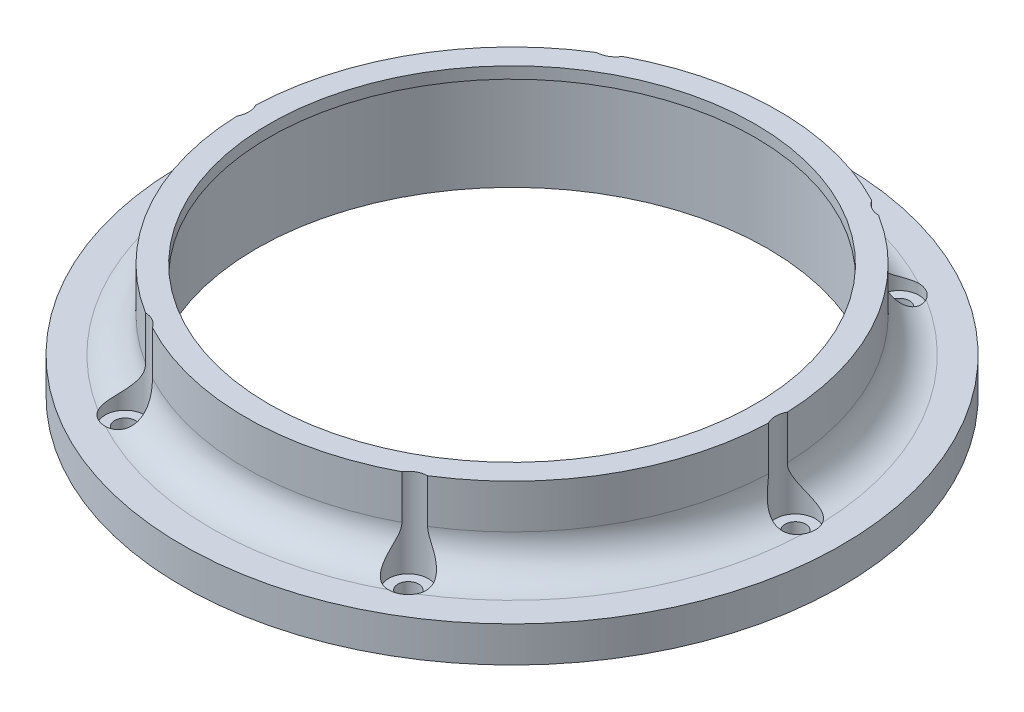
SolidWorks part; units mm, degrees
ref_plane "Front Plane" through (0, 0, 0) normal (0, 0, 1) x (1, 0, 0)
ref_plane "Top Plane" through (0, 0, 0) normal (0, 1, 0) x (1, 0, 0)
ref_plane "Right Plane" through (0, 0, 0) normal (1, 0, 0) x (0, 0, -1)
sketch "Sketch1" plane through (0, 0, 0) normal (0, 1, 0) x (1, 0, 0)
  circle A0 centre (0, 0) radius 61.25 construction
  circle A1 centre (0, 0) radius 55.25
  circle A2 centre (0, 0) radius 57.5
  dimension "D1" = 122.5
  dimension "D2" = 110.5
  dimension "D3" = 115
extrude "Boss-Extrude1" add sketch "Sketch1" along normal blind 22
sketch "Sketch2" plane through (0, 0, 0) normal (0, -1, 0) x (1, 0, 0)
  circle A0 centre (0, 0) radius 61.25 construction
  circle A1 centre (0, 0) radius 71.25
  circle A2 centre (0, 0) radius 57.5 construction
  circle A3 centre (0, 0) radius 57.5
  dimension "D1" = 122.5
  dimension "D2" = 10
extrude "Boss-Extrude2" add sketch "Sketch2" against normal blind 7.5
sketch "Sketch6" plane through (0, 7.5, 0) normal (0, 1, 0) x (1, 0, 0)
  circle A0 centre (0, 0) radius 61.25 construction
  point P0 (-61.25, 0)
  dimension "D1" = 122.5
hole_wizard "CBORE for M4 SBHCS1" positions "Sketch6" profile "Sketch5" counterbore size "M4" standard "ANSI Metric" end condition through all
sketch "Sketch5" plane through (-61.25, 7.5, 0) normal (1, 0, 0) x (0, 0, 1)
  line L0 (0, 0) -> (0, 7.5)
  line L1 (0, 7.5) -> (2.25, 7.5)
  line L3 (2.25, 7.5) -> (2.25, 2.2)
  line L4 (2.25, 2.2) -> (4.3, 2.2)
  line L5 (4.3, 2.2) -> (4.3, 0)
  line L7 (4.3, 0) -> (0, 0)
  line L11 (0, -6.35) -> (0, 107.95) construction
  dimension "Thru Hole Dia." = 4.5
  dimension "Thru Hole Depth" = 7.5
  dimension "C'Bore Dia." = 8.6
  dimension "C'Bore Depth" = 2.2
fillet "Fillet2" radius 7.5 1 edges at (57.5, 7.5, 0)
sketch "Sketch7" plane through (0, 7.5, 0) normal (0, 1, 0) x (1, 0, 0)
  circle A1 centre (-61.25, 0) radius 4.3
  circle A2 centre (-61.25, 0) radius 4.3
  dimension "D1" = 0
extrude "Cut-Extrude1" cut sketch "Sketch7" along normal through all
pattern_circular "CirPattern1" count 6 over 360 about axis through (0, 7.5, 0) along (0, -1, 0) of "Cut-Extrude1", "CBORE for M4 SBHCS1"
sketch "Sketch8" plane through (0, 22, 0) normal (0, 1, 0) x (1, 0, 0)
  circle A0 centre (0, 0) radius 52.5
  arc A12 (-57.4639, -2.0384) -> (-30.4972, -48.746) centre (0, 0) ccw
  arc A13 (-26.9666, -50.7844) -> (-30.4972, -48.746) centre (-30.625, -53.0441) ccw
  arc A14 (-26.9666, -50.7844) -> (26.9666, -50.7844) centre (0, 0) ccw
  arc A15 (30.4972, -48.746) -> (26.9666, -50.7844) centre (30.625, -53.0441) ccw
  arc A16 (30.4972, -48.746) -> (57.4639, -2.0384) centre (0, 0) ccw
  arc A17 (57.4639, 2.0384) -> (57.4639, -2.0384) centre (61.25, 0) ccw
  arc A18 (57.4639, 2.0384) -> (30.4972, 48.746) centre (0, 0) ccw
  arc A19 (26.9666, 50.7844) -> (30.4972, 48.746) centre (30.625, 53.0441) ccw
  arc A20 (26.9666, 50.7844) -> (-26.9666, 50.7844) centre (0, 0) ccw
  arc A21 (-30.4972, 48.746) -> (-26.9666, 50.7844) centre (-30.625, 53.0441) ccw
  arc A22 (-30.4972, 48.746) -> (-57.4639, 2.0384) centre (0, 0) ccw
  arc A23 (-57.4639, -2.0384) -> (-57.4639, 2.0384) centre (-61.25, 0) ccw
  arc A24 (-57.4639, -2.0384) -> (-30.4972, -48.746) centre (0, 0) ccw
  arc A25 (-26.9666, -50.7844) -> (-30.4972, -48.746) centre (-30.625, -53.0441) ccw
  arc A26 (-26.9666, -50.7844) -> (26.9666, -50.7844) centre (0, 0) ccw
  arc A27 (30.4972, -48.746) -> (26.9666, -50.7844) centre (30.625, -53.0441) ccw
  arc A28 (30.4972, -48.746) -> (57.4639, -2.0384) centre (0, 0) ccw
  arc A29 (57.4639, 2.0384) -> (57.4639, -2.0384) centre (61.25, 0) ccw
  arc A30 (57.4639, 2.0384) -> (30.4972, 48.746) centre (0, 0) ccw
  arc A31 (26.9666, 50.7844) -> (30.4972, 48.746) centre (30.625, 53.0441) ccw
  arc A32 (26.9666, 50.7844) -> (-26.9666, 50.7844) centre (0, 0) ccw
  arc A33 (-30.4972, 48.746) -> (-26.9666, 50.7844) centre (-30.625, 53.0441) ccw
  arc A34 (-30.4972, 48.746) -> (-57.4639, 2.0384) centre (0, 0) ccw
  arc A35 (-57.4639, -2.0384) -> (-57.4639, 2.0384) centre (-61.25, 0) ccw
  dimension "D2" = 5
  dimension "D1" = 0
extrude "Boss-Extrude3" add sketch "Sketch8" along normal blind 2.5
sketch "Sketch10" plane through (0, 0, 0) normal (0, -1, 0) x (1, 0, 0)
  circle A0 centre (0, 0) radius 55.25 construction
  circle A1 centre (0, 0) radius 71.25
  circle A2 centre (0, 0) radius 71.25
  circle A3 centre (61.25, 0) radius 2.25 construction
  circle A4 centre (30.625, 53.0441) radius 2.25 construction
  circle A5 centre (-30.625, 53.0441) radius 2.25 construction
  circle A6 centre (-61.25, 0) radius 2.25 construction
  circle A7 centre (-30.625, -53.0441) radius 2.25 construction
  circle A8 centre (30.625, -53.0441) radius 2.25 construction
  circle A9 centre (0, 0) radius 55.25
  circle A10 centre (61.25, 0) radius 2.25
  circle A11 centre (30.625, 53.0441) radius 2.25
  circle A12 centre (-30.625, 53.0441) radius 2.25
  circle A13 centre (-61.25, 0) radius 2.25
  circle A14 centre (-30.625, -53.0441) radius 2.25
  circle A15 centre (30.625, -53.0441) radius 2.25
  dimension "D1" = 0
extrude "Boss-Extrude4" add sketch "Sketch10" along normal blind 0.2
